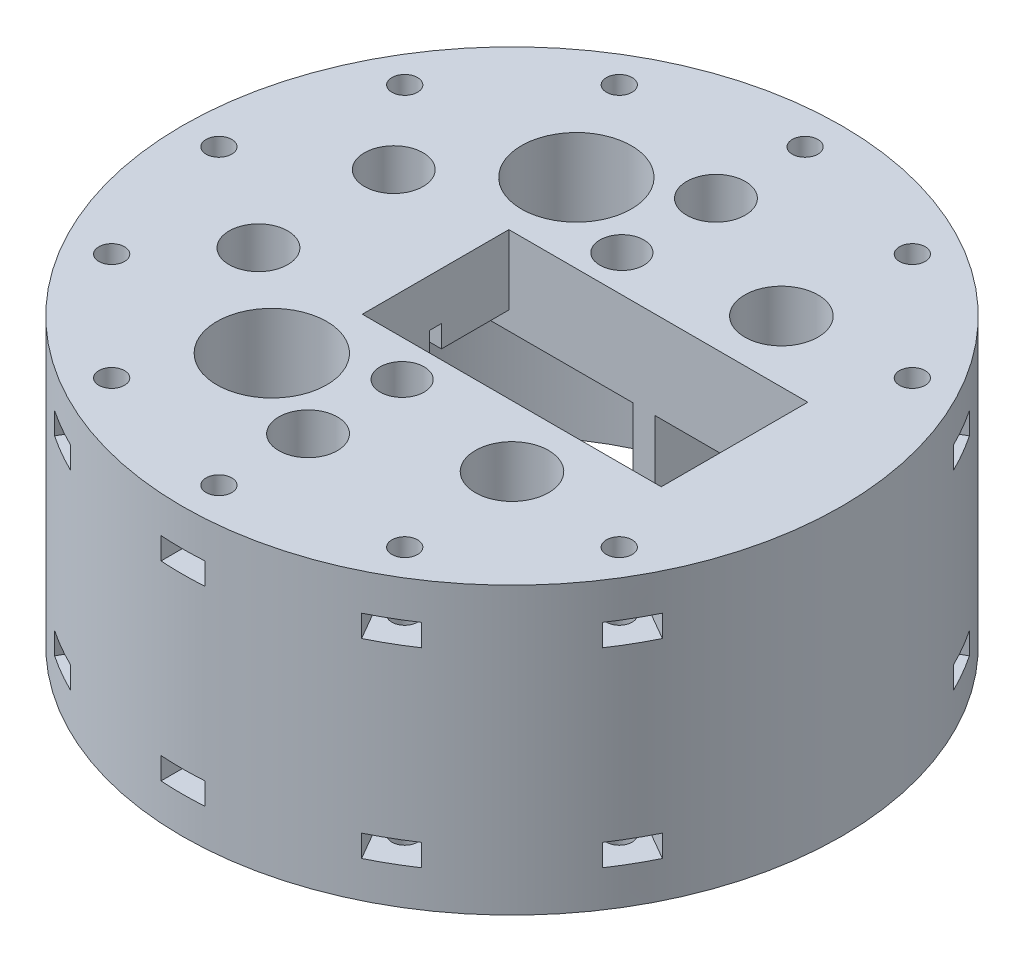
SolidWorks part; units mm, degrees
ref_plane "Front Plane" through (0, 0, 0) normal (0, 0, 1) x (1, 0, 0)
ref_plane "Top Plane" through (0, 0, 0) normal (0, 1, 0) x (1, 0, 0)
ref_plane "Right Plane" through (0, 0, 0) normal (1, 0, 0) x (0, 0, -1)
sketch "Sketch1" plane through (0, 0, 0) normal (0, 1, 0) x (1, 0, 0)
  line L0 (-43.0464, 0) -> (41.9462, 0) construction
  line L1 (0, 43.1152) -> (0, -41.8775) construction
  circle A1 centre (0, 0) radius 45
  dimension "D2" = 90
extrude "Boss-Extrude1" add sketch "Sketch1" along normal blind 39
sketch "Sketch2" plane through (0, 0, 0) normal (0, -1, 0) x (1, 0, 0)
  circle A0 centre (0, 0) radius 35
  dimension "D1" = 70
extrude "Cut-Extrude1" cut sketch "Sketch2" against normal blind 27
sketch "Sketch3" plane through (0, 27, 0) normal (0, -1, 0) x (1, 0, 0)
  line L0 (35, 0) -> (-35, 0) construction
  line L1 (0, -35) -> (0, 35) construction
  line L3 (37.5324, -10) -> (-17.4676, -10)
  line L4 (37.5324, -10) -> (37.5324, 10)
  line L5 (37.5324, 10) -> (-17.4676, 10)
  line L6 (-17.4676, -10) -> (-17.4676, 10)
  circle A0 centre (0, 0) radius 35 construction
  circle A1 centre (0, 0) radius 35 construction
  dimension "D1" = 20
  dimension "D2" = 55
  dimension "D3" = 10
  dimension "D4" = 37.5324
extrude "Cut-Extrude2" cut sketch "Sketch3" against normal blind 2.5 and the other way up to next
sketch "Sketch4" plane through (0, 29.5, 0) normal (0, -1, 0) x (1, 0, 0)
  line L0 (37.5324, 0) -> (-17.4676, 0) construction
  line L1 (37.5324, 10) -> (37.5324, -10) construction
  line L2 (-17.4676, 10) -> (-17.4676, -10) construction
  line L3 (0, -10) -> (0, 10) construction
  line L4 (-17.4676, -10) -> (33.541, -10) construction
  line L5 (33.541, 10) -> (-17.4676, 10) construction
  line L7 (30.3722, -10) -> (-10.4278, -10)
  line L8 (30.3722, -10) -> (30.3722, 10)
  line L9 (30.3722, 10) -> (-10.4278, 10)
  line L10 (-10.4278, -10) -> (-10.4278, 10)
  dimension "D1" = 20
  dimension "D2" = 40.8
  dimension "D3" = 30.3722
  dimension "D4" = 10
extrude "Cut-Extrude3" cut sketch "Sketch4" against normal blind 10.5
sketch "Sketch8" plane through (0, 27, 0) normal (0, -1, 0) x (1, 0, 0)
  line L0 (-17.4676, 0) -> (-35, 0) construction
  line L1 (-17.4676, 10) -> (-17.4676, -10) construction
  line L2 (8.0367, 10) -> (8.0367, 34.0648) construction
  line L3 (33.541, 10) -> (-17.4676, 10) construction
  line L4 (8.0367, -10) -> (8.0367, -29.3194) construction
  line L5 (-17.4676, -10) -> (33.541, -10) construction
  line L6 (6.5367, 10) -> (6.5367, 34.3842)
  line L7 (9.5367, 10) -> (9.5367, 33.6757)
  line L8 (9.5367, 10) -> (6.5367, 10)
  line L9 (9.5367, -10) -> (6.5367, -10)
  line L10 (6.5367, -10) -> (6.5367, -34.3842)
  line L11 (9.5367, -10) -> (9.5367, -33.6757)
  line L12 (-17.4676, 1.5) -> (-34.9678, 1.5)
  line L13 (-17.4676, -1.5) -> (-34.9678, -1.5)
  line L14 (-17.4676, 1.5) -> (-17.4676, -1.5)
  arc A0 (33.541, 10) -> (33.541, -10) centre (0, 0) ccw construction
  arc A1 (9.5367, 33.6757) -> (6.5367, 34.3842) centre (7.9531, 33.6757) ccw
  arc A2 (9.5367, -33.6757) -> (6.5367, -34.3842) centre (7.9531, -33.6757) cw
  arc A3 (-34.9678, 1.5) -> (-34.9678, -1.5) centre (-34.9678, 0) ccw
  dimension "D3" = 1.5
  dimension "D1" = 1.5
  dimension "D2" = 1.5
  dimension "D4" = 1.5
extrude "Boss-Extrude2" add sketch "Sketch8" along normal through all
sketch "Sketch13" plane through (0, 27, 0) normal (0, -1, 0) x (1, 0, 0)
  line L0 (0, 0) -> (0, 35) construction
  line L1 (0, 0) -> (-17.5, 30.3109) construction
  line L2 (0, 0) -> (-41.2446, 0) construction
  line L3 (-32.8892, 11.9707) -> (0, 0) construction
  line L5 (0, 0) -> (24.7487, 24.7487) construction
  arc A0 (6.5367, 34.3842) -> (-34.9678, 1.5) centre (0, 0) ccw construction
  circle A1 centre (-12, 20.7846) radius 7.5
  circle A2 centre (-25.3717, 9.2345) radius 4
  arc A3 (33.541, 10) -> (9.5367, 33.6757) centre (0, 0) ccw construction
  circle A4 centre (18.3848, 18.3848) radius 5
  circle A5 centre (18.3848, -18.3848) radius 5
  circle A6 centre (-12, -20.7846) radius 7.5
  circle A7 centre (-25.3717, -9.2345) radius 4
  circle A8 centre (0, -15) radius 3
  circle A9 centre (0, -27.8351) radius 4
  circle A10 centre (0, 27.8351) radius 4
  circle A11 centre (0, 15) radius 3
  dimension "D3" = 15
  dimension "D6" = 8
  dimension "D8" = 10
  dimension "D10" = 8
  dimension "D11" = 6
  dimension "D1" = 30
  dimension "D2" = 20
  dimension "D4" = 27
  dimension "D5" = 24
  dimension "D7" = 45
  dimension "D9" = 26
  dimension "D12" = 15
extrude "Cut-Extrude7" cut sketch "Sketch13" against normal through all
sketch "Sketch15" plane through (0, 0, -1.5) normal (0, 0, -1) x (-1, 0, 0)
  line L0 (34.9678, 0) -> (17.4676, 27)
  line L1 (17.4676, 27) -> (17.4676, 0)
  line L3 (17.4676, 0) -> (34.9678, 0)
extrude "Cut-Extrude8" cut sketch "Sketch15" against normal blind 3
sketch "Sketch16" plane through (0, 29.5, 0) normal (0, -1, 0) x (1, 0, 0)
  line L0 (-17.4676, 0) -> (37.5324, 0) construction
  line L1 (-17.4676, 10) -> (-17.4676, -10) construction
  line L2 (37.5324, -10) -> (37.5324, 10) construction
  line L3 (30.3722, -0.8) -> (37.5324, -0.8)
  line L4 (-10.4278, -0.8) -> (-17.4676, -0.8)
  line L5 (-10.4278, 10) -> (-10.4278, -10) construction
  line L6 (-10.4278, 0.8) -> (-17.4676, 0.8)
  line L7 (-17.4676, 0.8) -> (-17.4676, -0.8)
  line L8 (-10.4278, 0.8) -> (-10.4278, -0.8)
  line L9 (30.3722, -10) -> (30.3722, 10) construction
  line L10 (30.3722, 0.8) -> (37.5324, 0.8)
  line L11 (37.5324, 0.8) -> (37.5324, -0.8)
  line L12 (30.3722, 0.8) -> (30.3722, -0.8)
  dimension "D1" = 0.8
extrude "Cut-Extrude10" cut sketch "Sketch16" against normal blind 3
sketch "Sketch27" plane through (0, 0, 0) normal (0, -1, 0) x (1, 0, 0)
  line L0 (0, 0) -> (0, -53.17) construction
  line L1 (0, 0) -> (47.7582, -27.5732) construction
  line L3 (31.641, -18.2679) -> (31.641, -21.7321) construction
  line L4 (31.641, -21.7321) -> (34.641, -23.4641) construction
  line L5 (34.641, -23.4641) -> (37.641, -21.7321) construction
  line L6 (37.641, -21.7321) -> (37.641, -18.2679) construction
  line L7 (37.641, -18.2679) -> (34.641, -16.5359) construction
  line L8 (34.641, -16.5359) -> (31.641, -18.2679) construction
  circle A0 centre (0, 0) radius 40 construction
  circle A1 centre (34.641, -20) radius 1.75
  circle A2 centre (0, 0) radius 35 construction
  circle A3 centre (34.641, -20) radius 3 construction
  circle A4 centre (20, -34.641) radius 1.75
  circle A5 centre (0, -40) radius 1.75
  circle A6 centre (-20, -34.641) radius 1.75
  circle A7 centre (-34.641, -20) radius 1.75
  circle A8 centre (-40, 0) radius 1.75
  circle A9 centre (-34.641, 20) radius 1.75
  circle A10 centre (-20, 34.641) radius 1.75
  circle A11 centre (0, 40) radius 1.75
  circle A12 centre (20, 34.641) radius 1.75
  circle A13 centre (34.641, 20) radius 1.75
  circle A15 centre (40, 0) radius 1.75 [skipped]
  point P28 (0, 0)
  point P41 (0, 0)
  dimension "D1" = 80
  dimension "D3" = 3.5
  dimension "D4" = 70
  dimension "D5" = 6
  dimension "D6" = 12
  dimension "D2" = 60
extrude "Cut-Extrude15" cut sketch "Sketch27" against normal through all
ref_plane "Plane1" through (0, 34, 0) normal (0, 1, 0) x (1, 0, 0)
sketch "Sketch28" plane through (0, 34, 0) normal (0, 1, 0) x (1, 0, 0)
  line L0 (0, 0) -> (-54.493, 0) construction
  line L1 (-31.641, 18.2679) -> (-31.641, 21.7321)
  line L2 (-36.5359, 0) -> (-38.2679, 3)
  line L3 (-38.2679, 3) -> (-44.8999, 3)
  line L4 (-31.641, 21.7321) -> (-37.3844, 25.048)
  line L5 (-40.3844, 19.8519) -> (-34.641, 16.5359)
  line L6 (-44.8999, -3) -> (-38.2679, -3)
  line L7 (-38.2679, -3) -> (-36.5359, 0)
  line L8 (-43.4641, 0) -> (-42.5981, -1.5) [skipped]
  line L9 (-41.7321, 3) -> (-42.5981, 1.5) [skipped]
  line L10 (-34.641, 16.5359) -> (-31.641, 18.2679)
  line L11 (-18.2679, 31.641) -> (-16.5359, 34.641)
  line L12 (-16.5359, 34.641) -> (-19.8519, 40.3844)
  line L13 (-25.048, 37.3844) -> (-21.7321, 31.641)
  line L14 (-21.7321, 31.641) -> (-18.2679, 31.641)
  line L15 (0, 36.5359) -> (3, 38.2679)
  line L16 (3, 38.2679) -> (3, 44.8999)
  line L17 (-3, 44.8999) -> (-3, 38.2679)
  line L18 (-3, 38.2679) -> (0, 36.5359)
  line L19 (18.2679, 31.641) -> (21.7321, 31.641)
  line L20 (21.7321, 31.641) -> (25.048, 37.3844)
  line L21 (19.8519, 40.3844) -> (16.5359, 34.641)
  line L22 (16.5359, 34.641) -> (18.2679, 31.641)
  line L23 (31.641, 18.2679) -> (34.641, 16.5359)
  line L24 (34.641, 16.5359) -> (40.3844, 19.8519)
  line L25 (37.3844, 25.048) -> (31.641, 21.7321)
  line L26 (31.641, 21.7321) -> (31.641, 18.2679)
  line L31 (31.641, -18.2679) -> (31.641, -21.7321)
  line L32 (31.641, -21.7321) -> (37.3844, -25.048)
  line L33 (40.3844, -19.8519) -> (34.641, -16.5359)
  line L34 (34.641, -16.5359) -> (31.641, -18.2679)
  line L35 (18.2679, -31.641) -> (16.5359, -34.641)
  line L36 (16.5359, -34.641) -> (19.8519, -40.3844)
  line L37 (25.048, -37.3844) -> (21.7321, -31.641)
  line L38 (21.7321, -31.641) -> (18.2679, -31.641)
  line L39 (0, -36.5359) -> (-3, -38.2679)
  line L40 (-3, -38.2679) -> (-3, -44.8999)
  line L41 (3, -44.8999) -> (3, -38.2679)
  line L42 (3, -38.2679) -> (0, -36.5359)
  line L43 (-18.2679, -31.641) -> (-21.7321, -31.641)
  line L44 (-21.7321, -31.641) -> (-25.048, -37.3844)
  line L45 (-19.8519, -40.3844) -> (-16.5359, -34.641)
  line L46 (-16.5359, -34.641) -> (-18.2679, -31.641)
  line L47 (-31.641, -18.2679) -> (-34.641, -16.5359)
  line L48 (-34.641, -16.5359) -> (-40.3844, -19.8519)
  line L49 (-37.3844, -25.048) -> (-31.641, -21.7321)
  line L50 (-31.641, -21.7321) -> (-31.641, -18.2679)
  line L51 (36.5359, 0) -> (38.2679, -3) [skipped]
  line L52 (38.2679, -3) -> (44.8999, -3) [skipped]
  line L53 (44.8999, 3) -> (38.2679, 3) [skipped]
  line L54 (38.2679, 3) -> (36.5359, 0) [skipped]
  arc A0 (-44.8999, 3) -> (-44.8999, -3) centre (0, 0) ccw
  circle A1 centre (-40, 0) radius 3 construction
  arc A2 (-37.3844, 25.048) -> (-40.3844, 19.8519) centre (0, 0) ccw
  circle A3 centre (-34.641, 20) radius 3 construction
  arc A4 (-19.8519, 40.3844) -> (-25.048, 37.3844) centre (0, 0) ccw
  circle A5 centre (-20, 34.641) radius 3 construction
  arc A6 (3, 44.8999) -> (-3, 44.8999) centre (0, 0) ccw
  circle A7 centre (0, 40) radius 3 construction
  arc A8 (25.048, 37.3844) -> (19.8519, 40.3844) centre (0, 0) ccw
  circle A9 centre (20, 34.641) radius 3 construction
  arc A10 (40.3844, 19.8519) -> (37.3844, 25.048) centre (0, 0) ccw
  circle A11 centre (34.641, 20) radius 3 construction
  arc A14 (37.3844, -25.048) -> (40.3844, -19.8519) centre (0, 0) ccw
  circle A15 centre (34.641, -20) radius 3 construction
  arc A16 (19.8519, -40.3844) -> (25.048, -37.3844) centre (0, 0) ccw
  circle A17 centre (20, -34.641) radius 3 construction
  arc A18 (-3, -44.8999) -> (3, -44.8999) centre (0, 0) ccw
  circle A19 centre (0, -40) radius 3 construction
  arc A20 (-25.048, -37.3844) -> (-19.8519, -40.3844) centre (0, 0) ccw
  circle A21 centre (-20, -34.641) radius 3 construction
  arc A22 (-40.3844, -19.8519) -> (-37.3844, -25.048) centre (0, 0) ccw
  circle A23 centre (-34.641, -20) radius 3 construction
  arc A24 (44.8999, -3) -> (44.8999, 3) centre (0, 0) ccw [skipped]
  circle A25 centre (40, 0) radius 3 construction
  point P94 (0, 0)
  dimension "D1" = 90
  dimension "D2" = 6
  dimension "D3" = 12
extrude "Cut-Extrude17" cut sketch "Sketch28" against normal blind 3
ref_plane "Plane2" through (0, 5, 0) normal (0, -1, 0) x (-1, 0, 0)
sketch "Sketch30" plane through (0, 5, 0) normal (0, -1, 0) x (-1, 0, 0)
  line L0 (0, 0) -> (56.1913, 0) construction
  line L1 (31.641, -18.2679) -> (31.641, -21.7321)
  line L2 (36.5359, 0) -> (38.2679, -3)
  line L3 (38.2679, -3) -> (44.8999, -3)
  line L4 (31.641, -21.7321) -> (37.3844, -25.048)
  line L5 (40.3844, -19.8519) -> (34.641, -16.5359)
  line L6 (44.8999, 3) -> (38.2679, 3)
  line L7 (38.2679, 3) -> (36.5359, 0)
  line L8 (43.4641, 0) -> (42.5981, 1.5) [skipped]
  line L9 (41.7321, -3) -> (42.5981, -1.5) [skipped]
  line L10 (34.641, -16.5359) -> (31.641, -18.2679)
  line L11 (18.2679, -31.641) -> (16.5359, -34.641)
  line L12 (16.5359, -34.641) -> (19.8519, -40.3844)
  line L13 (25.048, -37.3844) -> (21.7321, -31.641)
  line L14 (21.7321, -31.641) -> (18.2679, -31.641)
  line L15 (0, -36.5359) -> (-3, -38.2679)
  line L16 (-3, -38.2679) -> (-3, -44.8999)
  line L17 (3, -44.8999) -> (3, -38.2679)
  line L18 (3, -38.2679) -> (0, -36.5359)
  line L19 (-18.2679, -31.641) -> (-21.7321, -31.641)
  line L20 (-21.7321, -31.641) -> (-25.048, -37.3844)
  line L21 (-19.8519, -40.3844) -> (-16.5359, -34.641)
  line L22 (-16.5359, -34.641) -> (-18.2679, -31.641)
  line L23 (-31.641, -18.2679) -> (-34.641, -16.5359)
  line L24 (-34.641, -16.5359) -> (-40.3844, -19.8519)
  line L25 (-37.3844, -25.048) -> (-31.641, -21.7321)
  line L26 (-31.641, -21.7321) -> (-31.641, -18.2679)
  line L31 (-31.641, 18.2679) -> (-31.641, 21.7321)
  line L32 (-31.641, 21.7321) -> (-37.3844, 25.048)
  line L33 (-40.3844, 19.8519) -> (-34.641, 16.5359)
  line L34 (-34.641, 16.5359) -> (-31.641, 18.2679)
  line L35 (-18.2679, 31.641) -> (-16.5359, 34.641)
  line L36 (-16.5359, 34.641) -> (-19.8519, 40.3844)
  line L37 (-25.048, 37.3844) -> (-21.7321, 31.641)
  line L38 (-21.7321, 31.641) -> (-18.2679, 31.641)
  line L39 (0, 36.5359) -> (3, 38.2679)
  line L40 (3, 38.2679) -> (3, 44.8999)
  line L41 (-3, 44.8999) -> (-3, 38.2679)
  line L42 (-3, 38.2679) -> (0, 36.5359)
  line L43 (18.2679, 31.641) -> (21.7321, 31.641)
  line L44 (21.7321, 31.641) -> (25.048, 37.3844)
  line L45 (19.8519, 40.3844) -> (16.5359, 34.641)
  line L46 (16.5359, 34.641) -> (18.2679, 31.641)
  line L47 (31.641, 18.2679) -> (34.641, 16.5359)
  line L48 (34.641, 16.5359) -> (40.3844, 19.8519)
  line L49 (37.3844, 25.048) -> (31.641, 21.7321)
  line L50 (31.641, 21.7321) -> (31.641, 18.2679)
  line L51 (-36.5359, 0) -> (-38.2679, 3) [skipped]
  line L52 (-38.2679, 3) -> (-44.8999, 3) [skipped]
  line L53 (-44.8999, -3) -> (-38.2679, -3) [skipped]
  line L54 (-38.2679, -3) -> (-36.5359, 0) [skipped]
  arc A0 (44.8999, -3) -> (44.8999, 3) centre (0, 0) ccw
  circle A1 centre (40, 0) radius 3 construction
  arc A2 (37.3844, -25.048) -> (40.3844, -19.8519) centre (0, 0) ccw
  circle A3 centre (34.641, -20) radius 3 construction
  arc A4 (19.8519, -40.3844) -> (25.048, -37.3844) centre (0, 0) ccw
  circle A5 centre (20, -34.641) radius 3 construction
  arc A6 (-3, -44.8999) -> (3, -44.8999) centre (0, 0) ccw
  circle A7 centre (0, -40) radius 3 construction
  arc A8 (-25.048, -37.3844) -> (-19.8519, -40.3844) centre (0, 0) ccw
  circle A9 centre (-20, -34.641) radius 3 construction
  arc A10 (-40.3844, -19.8519) -> (-37.3844, -25.048) centre (0, 0) ccw
  circle A11 centre (-34.641, -20) radius 3 construction
  arc A14 (-37.3844, 25.048) -> (-40.3844, 19.8519) centre (0, 0) ccw
  circle A15 centre (-34.641, 20) radius 3 construction
  arc A16 (-19.8519, 40.3844) -> (-25.048, 37.3844) centre (0, 0) ccw
  circle A17 centre (-20, 34.641) radius 3 construction
  arc A18 (3, 44.8999) -> (-3, 44.8999) centre (0, 0) ccw
  circle A19 centre (0, 40) radius 3 construction
  arc A20 (25.048, 37.3844) -> (19.8519, 40.3844) centre (0, 0) ccw
  circle A21 centre (20, 34.641) radius 3 construction
  arc A22 (40.3844, 19.8519) -> (37.3844, 25.048) centre (0, 0) ccw
  circle A23 centre (34.641, 20) radius 3 construction
  arc A24 (-44.8999, 3) -> (-44.8999, -3) centre (0, 0) ccw [skipped]
  circle A25 centre (-40, 0) radius 3 construction
  point P94 (0, 0)
  dimension "D1" = 90
  dimension "D2" = 6
  dimension "D3" = 12
extrude "Cut-Extrude19" cut sketch "Sketch30" against normal blind 3
